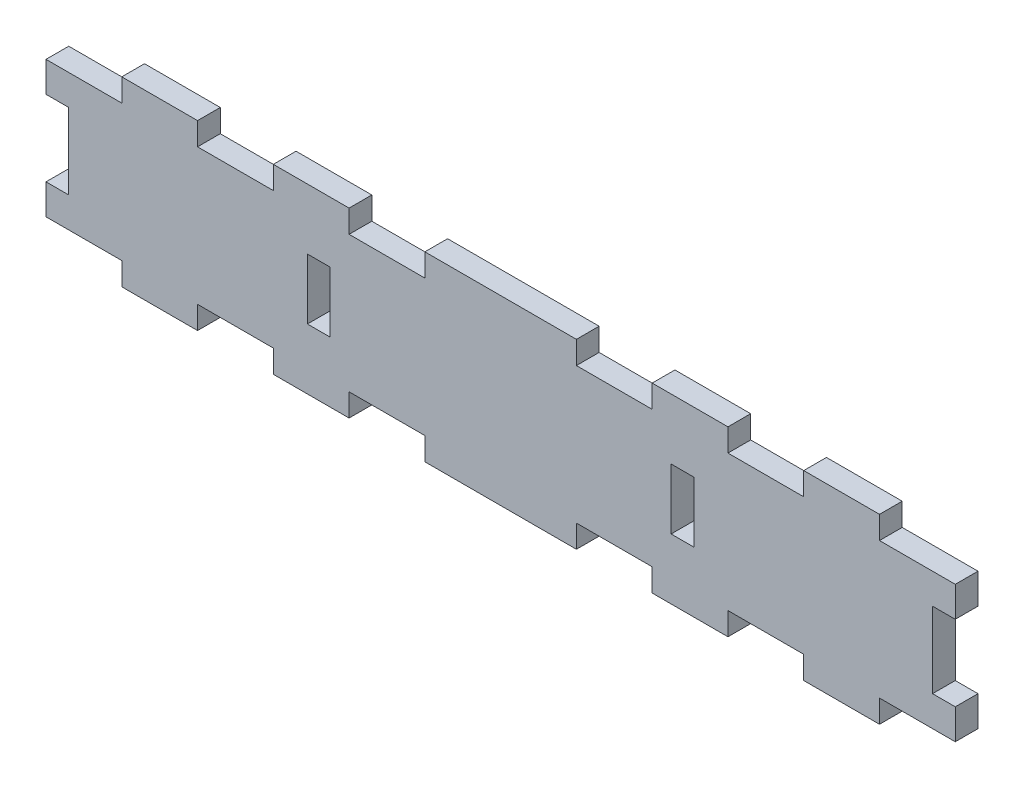
SolidWorks part; units mm, degrees
material "PC High Viscosity"
ref_plane "Front Plane" through (0, 0, 0) normal (0, 0, 1) x (1, 0, 0)
ref_plane "Top Plane" through (0, 0, 0) normal (0, 1, 0) x (1, 0, 0)
ref_plane "Right Plane" through (0, 0, 0) normal (1, 0, 0) x (0, 0, -1)
sketch "Sketch1" plane through (0, 0, 0) normal (0, 0, 1) x (1, 0, 0)
  line L1 (-60, -12) -> (60, -12)
  line L2 (-60, -12) -> (-60, 12)
  line L3 (-60, 12) -> (60, 12)
  line L4 (60, -12) -> (60, 12)
  line L5 (-60, -12) -> (60, 12) construction
  line L6 (-60, 12) -> (60, -12) construction
  point P0 (0, 0)
  dimension "D1" = 120
  dimension "D2" = 24
extrude "Boss-Extrude1" add sketch "Sketch1" along normal blind 3
sketch "Sketch2" plane through (0, 0, 3) normal (0, 0, 1) x (1, 0, 0)
  line L0 (60, -12) -> (60, 12) construction
  line L1 (60, 12) -> (-60, 12) construction
  line L3 (20, 12) -> (30, 12) construction
  line L4 (10, 12) -> (20, 12)
  line L5 (10, 12) -> (10, 9)
  line L6 (10, 9) -> (20, 9)
  line L7 (20, 12) -> (20, 9)
  line L8 (30, 12) -> (40, 12)
  line L9 (30, 12) -> (30, 9)
  line L10 (30, 9) -> (40, 9)
  line L11 (40, 12) -> (40, 9)
  line L12 (50, 12) -> (60, 12)
  line L13 (50, 12) -> (50, 9)
  line L14 (50, 9) -> (60, 9)
  line L15 (60, 12) -> (60, 9)
  line L16 (40, 12) -> (50, 12) construction
  dimension "D1" = 10
  dimension "D2" = 3
extrude "Cut-Extrude1" cut sketch "Sketch2" against normal through all
mirror "Mirror2" about plane through (0, 0, 0) normal (1, 0, 0) of "Cut-Extrude1"
mirror "Mirror3" about plane through (0, 0, 0) normal (0, 1, 0) of "Mirror2"
sketch "Sketch3" plane through (0, 0, 3) normal (0, 0, 1) x (1, 0, 0)
  line L0 (0, -12) -> (0, 12) construction
  line L1 (-10, -12) -> (10, -12) construction
  line L2 (10, 12) -> (-10, 12) construction
  line L3 (60, 0) -> (-60, 0) construction
  line L4 (22.5, 4) -> (25.5, 4)
  line L5 (22.5, 4) -> (22.5, -4)
  line L6 (22.5, -4) -> (25.5, -4)
  line L7 (25.5, 4) -> (25.5, -4)
  line L8 (60, -9) -> (60, 9) construction
  line L9 (-60, 9) -> (-60, -9) construction
  line L10 (-25.5, 4) -> (-25.5, -4)
  line L11 (-22.5, -4) -> (-25.5, -4)
  line L12 (-22.5, 4) -> (-22.5, -4)
  line L13 (-22.5, 4) -> (-25.5, 4)
  line L14 (57, 5) -> (57, -5)
  line L15 (-60, 5) -> (-57, 5)
  line L16 (-60, 5) -> (-60, -5)
  line L17 (-60, -5) -> (-57, -5)
  line L18 (-57, 5) -> (-57, -5)
  line L19 (60, -5) -> (57, -5)
  line L20 (60, 5) -> (60, -5)
  line L21 (60, 5) -> (57, 5)
  dimension "D1" = 3
  dimension "D2" = 8
  dimension "D3" = 45
  dimension "D4" = 10
extrude "Cut-Extrude2" cut sketch "Sketch3" against normal through all
equation "\"pulley_pitch_diam\"= 12.73mm"
equation "\"pulley_total_width\"= 16mm"
equation "\"pulley_total_diam\"= 16mm"
equation "\"belt_width\"= 6mm"
equation "\"material_thickness\"= 3mm"
equation "\"shaft_diam\"= 8mm"
equation "\"bearing_od\"= 22mm"
equation "\"bearing_thickness\"= 7mm"
equation "\"D1@Boss-Extrude1\"=\"material_thickness\""
equation "\"D2@Sketch2\"=\"material_thickness\""
equation "\"D1@Sketch3\"=\"material_thickness\""
